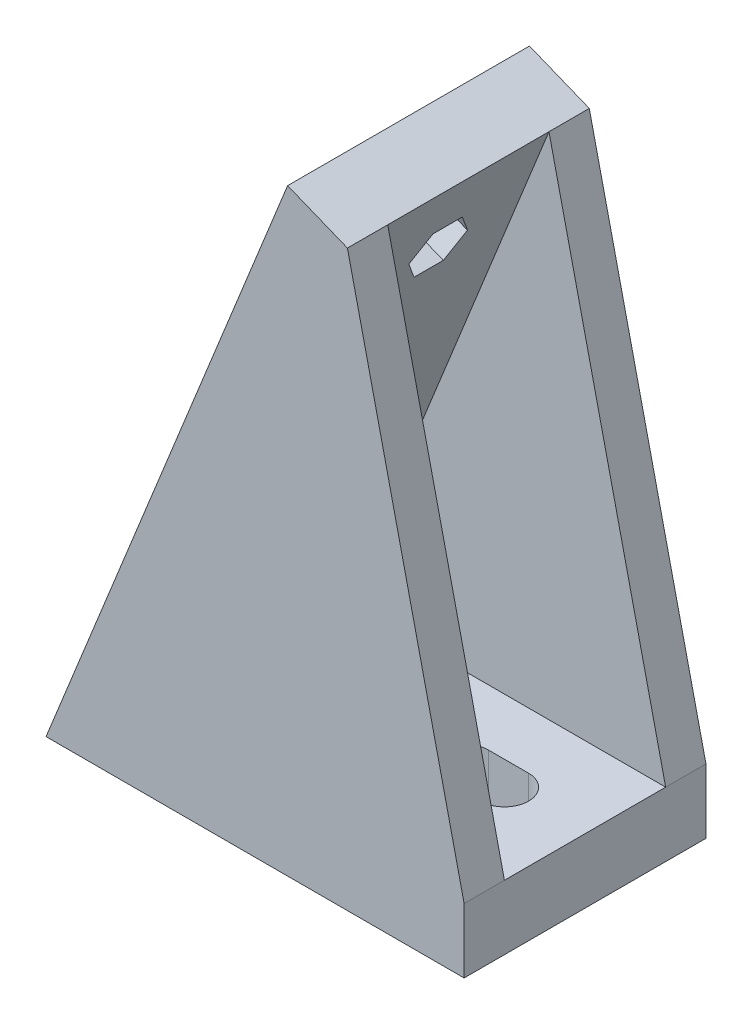
SolidWorks part; units mm, degrees
ref_plane "Front Plane" through (0, 0, 0) normal (0, 0, 1) x (1, 0, 0)
ref_plane "Top Plane" through (0, 0, 0) normal (0, 1, 0) x (1, 0, 0)
ref_plane "Right Plane" through (0, 0, 0) normal (1, 0, 0) x (0, 0, -1)
sketch "Sketch1" plane through (0, 0, 0) normal (0, 0, 1) x (1, 0, 0)
  line L0 (0, 0) -> (29.9685, 74.1747)
  line L4 (11.8605, 8) -> (37.386, 71.1779)
  line L5 (37.386, 71.1779) -> (29.9685, 74.1747)
  line L9 (0, 0) -> (51.8605, 0)
  line L13 (51.8605, 0) -> (51.8605, 8)
  line L15 (11.8605, 8) -> (51.8605, 8)
  dimension "D1" = 68
  dimension "D2" = 8
  dimension "D3" = 8
  dimension "D4" = 80
  dimension "D6" = 40
extrude "Boss-Extrude1" add sketch "Sketch1" along normal mid plane 30
sketch "Sketch2" plane through (0.3799, 8, 0) normal (0, 1, 0) x (1, 0, 0)
  line L0 (41.4805, 0) -> (36.4805, 0) construction
  line L1 (41.4805, -3) -> (36.4805, -3)
  line L2 (41.4805, 3) -> (36.4805, 3)
  line L4 (51.4805, -15) -> (51.4805, 15) construction
  arc A0 (41.4805, -3) -> (41.4805, 3) centre (41.4805, 0) ccw
  arc A1 (36.4805, 3) -> (36.4805, -3) centre (36.4805, 0) ccw
  point P3 (38.9805, 0)
  dimension "D3" = 3
  dimension "D1" = 5
  dimension "D2" = 10
extrude "Cut-Extrude1" cut sketch "Sketch2" against normal through all
sketch "Sketch3" plane through (7.4175, -2.9969, 0) normal (0.9272, -0.3746, 0) x (0, 0, -1)
sketch "Sketch4" plane through (0, 0, 15) normal (0, 0, 1) x (1, 0, 0)
  line L0 (37.386, 71.1779) -> (51.8605, 8)
  line L1 (51.8605, 0) -> (51.8605, 8) construction
  line L2 (51.8605, 8) -> (11.8605, 8) construction
rib "Rib1" sketch "Sketch4" sketch "Sketch4" thickness 5 extrusion direction parallel to sketch draft on no parameters "D1"=5
mirror "Mirror1" about plane through (0, 0, 0) normal (0, 0, 1) of "Rib1"
sketch "Sketch6" plane through (7.4175, -2.9969, 0) normal (0.9272, -0.3746, 0) x (0, 0, -1)
  line L0 (-10, 80) -> (10, 80) construction
  point P0 (0, 70)
  point P2 (0, 25)
  point P9 (0, 80)
  dimension "D1" = 10
  dimension "D2" = 45
hole_wizard "M3 Clearance Hole1" positions "Sketch6" profile "Sketch7" hole size "M3" standard "ANSI Metric" end condition through all
sketch "Sketch7" plane through (33.6399, 61.906, 0) normal (0, 0, 1) x (0.3746, 0.9272, 0)
  line L0 (0, 0) -> (0, 35.7863)
  line L1 (0, 35.7863) -> (1.7, 35.7863)
  line L2 (1.7, 35.7863) -> (1.7, 0.025)
  line L3 (1.7, 0.025) -> (1.725, 0)
  line L5 (1.725, 0) -> (0, 0)
  line L6 (-1.7, 0.025) -> (-1.725, 0) construction
  line L11 (0, -6.35) -> (0, 107.95) construction
  dimension "Thru Hole Dia." = 3.4
  dimension "Thru Hole Depth" = 35.7863
  dimension "Near C'Sink Dia." = 3.45
  dimension "Near C'Sink Angle" = 90
sketch "Sketch8" plane through (7.4175, -2.9969, 0) normal (0.9272, -0.3746, 0) x (0, 0, -1)
  line L1 (3.6373, 70) -> (1.8187, 73.15)
  line L2 (1.8187, 73.15) -> (-1.8187, 73.15)
  line L3 (-1.8187, 73.15) -> (-3.6373, 70)
  line L4 (-3.6373, 70) -> (-1.8187, 66.85)
  line L5 (-1.8187, 66.85) -> (1.8187, 66.85)
  line L6 (1.8187, 66.85) -> (3.6373, 70)
  line L7 (3.6373, 25) -> (1.8187, 28.15)
  line L8 (1.8187, 28.15) -> (-1.8187, 28.15)
  line L9 (-1.8187, 28.15) -> (-3.6373, 25)
  line L10 (-3.6373, 25) -> (-1.8187, 21.85)
  line L11 (-1.8187, 21.85) -> (1.8187, 21.85)
  line L12 (1.8187, 21.85) -> (3.6373, 25)
  circle A0 centre (0, 70) radius 3.15 construction
  circle A1 centre (0, 25) radius 3.15 construction
  dimension "D1" = 6.3
extrude "Cut-Extrude2" cut sketch "Sketch8" against normal blind 3
fillet "Fillet1" radius 10 1 edges at (11.8605, 8, 0)
